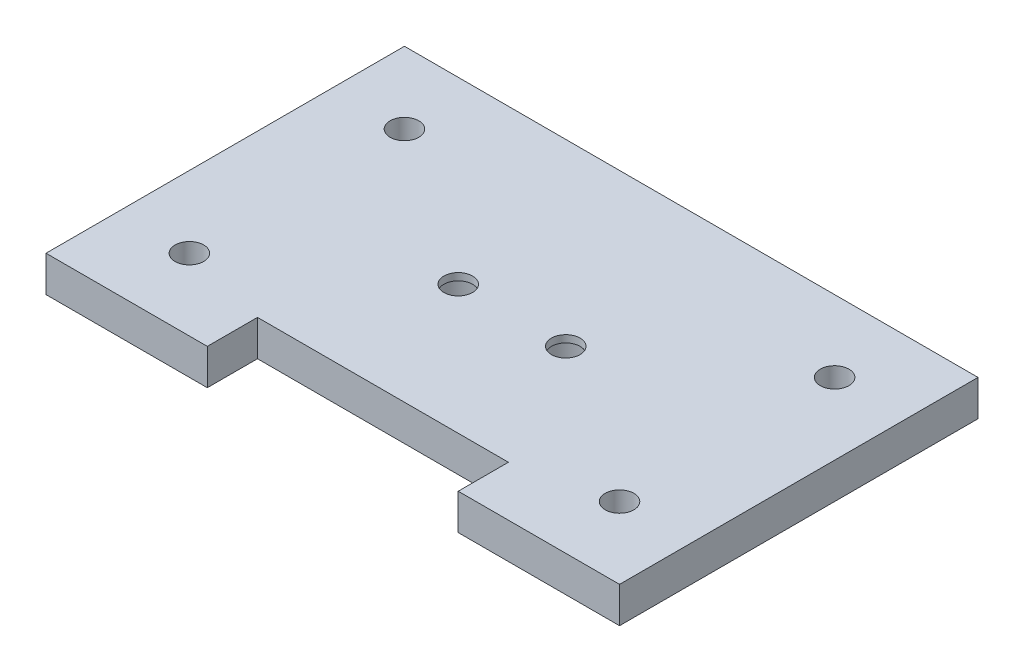
SolidWorks part; units mm, degrees
ref_plane "Front Plane" through (0, 0, 0) normal (0, 0, 1) x (1, 0, 0)
ref_plane "Top Plane" through (0, 0, 0) normal (0, 1, 0) x (1, 0, 0)
ref_plane "Right Plane" through (0, 0, 0) normal (1, 0, 0) x (0, 0, -1)
sketch "Sketch1" plane through (0, 0, 0) normal (0, 1, 0) x (1, 0, 0)
  line L0 (-17.5, -25) -> (17.5, -25)
  line L1 (-40, 25) -> (40, 25)
  line L2 (-40, 25) -> (-40, -25)
  line L3 (-40, -25) -> (40, -25)
  line L4 (40, 25) -> (40, -25)
  line L5 (-40, 25) -> (40, -25) construction
  line L6 (-40, -25) -> (40, 25) construction
  line L7 (-17.5, -25) -> (-17.5, -18)
  line L8 (17.5, -25) -> (17.5, -18)
  line L9 (-17.5, -18) -> (17.5, -18)
  line L10 (0, 25) -> (0, -25) construction
  line L11 (0, -18) -> (0, -25) construction
  circle A0 centre (-30, 15) radius 2
  circle A1 centre (30, 15) radius 2
  circle A2 centre (30, -15) radius 2
  circle A3 centre (-30, -15) radius 2
  point P0 (0, 0)
  point P24 (0, 0)
  dimension "D3" = 4
  dimension "D1" = 80
  dimension "D2" = 50
  dimension "D4" = 10
  dimension "D5" = 10
  dimension "D8" = 30
  dimension "D9" = 60
  dimension "D10" = 7
  dimension "D11" = 35
  dimension "D6" = 2
  dimension "D7" = 2
extrude "Boss-Extrude1" add sketch "Sketch1" along normal blind 5 contours L7 L9 L8 L3 L4 L1 L2 A3 A2 A1 A0 region at (0, 0, -1.4218)
sketch "Sketch2" plane through (0, 0, 0) normal (0, -1, 0) x (1, 0, 0)
  line L0 (-7.5, 0) -> (7.5, 0) construction
  circle A0 centre (-7.5, 0) radius 4
  circle A1 centre (7.5, 0) radius 4
  circle A2 centre (-7.5, 0) radius 2
  circle A3 centre (7.5, 0) radius 2
  point P4 (0, 0)
  dimension "D2" = 8
  dimension "D3" = 8
  dimension "D4" = 4
  dimension "D5" = 4
  dimension "D1" = 15
extrude "Cut-Extrude1" cut sketch "Sketch2" against normal blind 4 contours A2 | A2 A0 | A3 | A1 A3 region at (-11.3869, 0, 0) region at (3.6131, 0, 0) region at (-7.5, 0, 0) region at (7.5, 0, 0)
extrude "Cut-Extrude2" cut sketch "Sketch2<4>" against normal through all contours A2 | A3 region at (-7.5, 0, 0) region at (7.5, 0, 0)
sketch "Sketch2<4>" plane through (0, 0, 0) normal (0, -1, 0) x (1, 0, 0) same geometry as "Sketch2"
